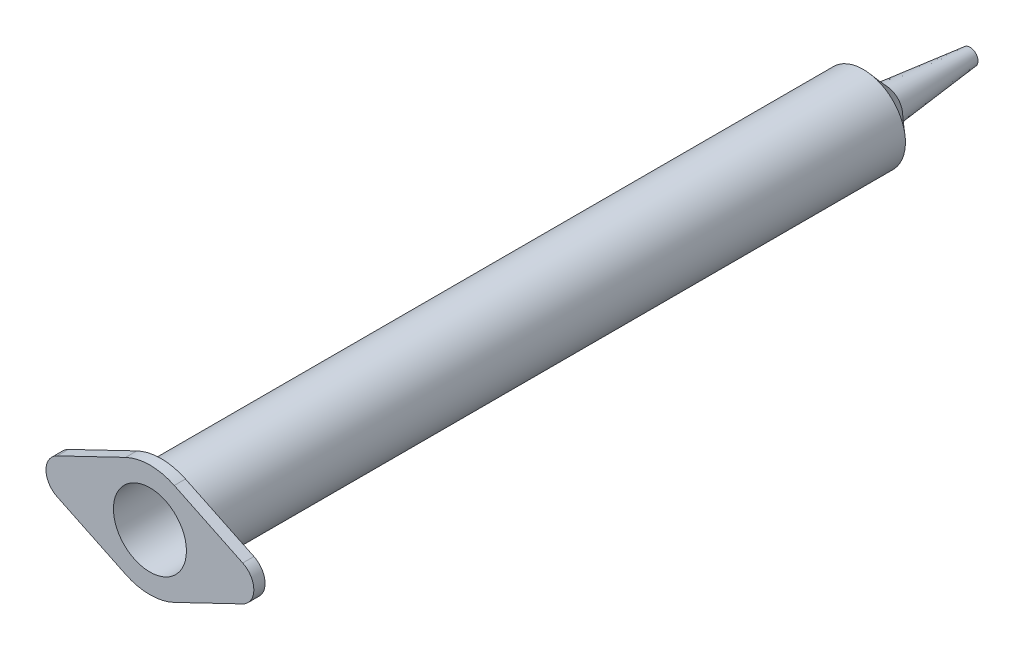
SolidWorks part; units mm, degrees
ref_plane "Front Plane" through (0, 0, 0) normal (0, 0, 1) x (1, 0, 0)
ref_plane "Top Plane" through (0, 0, 0) normal (0, 1, 0) x (1, 0, 0)
ref_plane "Right Plane" through (0, 0, 0) normal (1, 0, 0) x (0, 0, -1)
sketch "Sketch1" plane through (0, 0, 0) normal (0, 1, 0) x (1, 0, 0)
  line L0 (0, 25.6295) -> (0, -26.3849) construction
  line L1 (0, 0) -> (-10, 0)
  line L2 (-10, 0) -> (-10, 2)
  line L3 (-10, 2) -> (-7.5, 2)
  line L4 (-7.5, 2) -> (-7.5, 127)
  line L5 (-7.5, 127) -> (0, 127)
  line L6 (0, 127) -> (0, 0)
  dimension "D1" = 7.5
  dimension "D2" = 10
  dimension "D3" = 2
  dimension "D4" = 125
revolve "Revolve1" add sketch "Sketch1" angle 360 about L0
ref_plane "Plane1" through (0, 0, -131) normal (0, 0, -1) x (-1, 0, 0)
sketch "Sketch2" plane through (0, 0, -131) normal (0, 0, -1) x (-1, 0, 0)
  circle A0 centre (0, 0) radius 3
  dimension "D1" = 6
extrude "Boss-Extrude1" add sketch "Sketch2" along normal blind 15 draft 6 contours A0
sketch "Sketch5" plane through (0, 0, 0) normal (1, 0, 0) x (0, 0, -1)
  line L0 (129.9163, 0) -> (127.5505, 6.5)
  line L1 (0, 0) -> (129.9163, 0)
  line L2 (0, 0) -> (0, 6.5)
  line L3 (0, 6.5) -> (127.5505, 6.5)
  dimension "D1" = 70
  dimension "D2" = 6.5
sketch "Sketch7" plane through (0, 0, 0) normal (1, 0, 0) x (0, 0, -1)
  line L0 (160.6806, 0) -> (127.7298, 0) construction
  line L1 (127.7298, 0) -> (147.9588, 0)
  line L2 (147.9588, 0) -> (147.9588, 0.9574)
  line L3 (147.9588, 0.9574) -> (127.7298, 3.0835)
  line L4 (127.7298, 3.0835) -> (127.7298, 0)
  dimension "D1" = 6
revolve "Cut-Revolve2" cut sketch "Sketch7" angle 360 about L0
loft "Loft2" add section edge at (-7.5, 0, -127) section edge at (-3, 0, -131) connector at (-6.7248, 3.3207, -127) connector at (-2.229, 2.0079, -131)
revolve "Cut-Revolve3" cut sketch "Sketch5" angle 360 about L1
sketch "Sketch9" plane through (0, 0, 0) normal (0, 0, 1) x (1, 0, 0)
  circle A0 centre (0, 0) radius 1.1633
extrude "Cut-Extrude1" cut sketch "Sketch9" against normal through all
sketch "Sketch8" plane through (0, 0, 0) normal (0, 0, 1) x (1, 0, 0)
  line L0 (0, 10.7669) -> (0, 0) construction
  line L1 (0, 0) -> (-15, 0) construction
  line L2 (-4.3333, 9.0123) -> (-16.5167, 3.1543)
  line L3 (-16.5167, -3.1543) -> (-4.3333, -9.0123)
  line L4 (16.5167, -3.1543) -> (4.3333, -9.0123)
  line L5 (4.3333, 9.0123) -> (16.5167, 3.1543)
  arc A0 (-16.5167, 3.1543) -> (-16.5167, -3.1543) centre (-15, 0) ccw
  arc A1 (16.5167, 3.1543) -> (16.5167, -3.1543) centre (15, 0) cw
  circle A2 centre (0, 0) radius 10 construction
  circle A3 centre (0, 0) radius 10
  circle M6 centre (0, 0) radius 10
  dimension "D1" = 7
  dimension "D2" = 15
extrude "Boss-Extrude3" add sketch "Sketch8" against normal up to surface (2 mm away) contours L2 A0 L3 M6 | A1 L5 L4 M6 region at (-12.7135, 0, 0) region at (12.7135, 0, 0) up to face at (-10, 0, -2)
